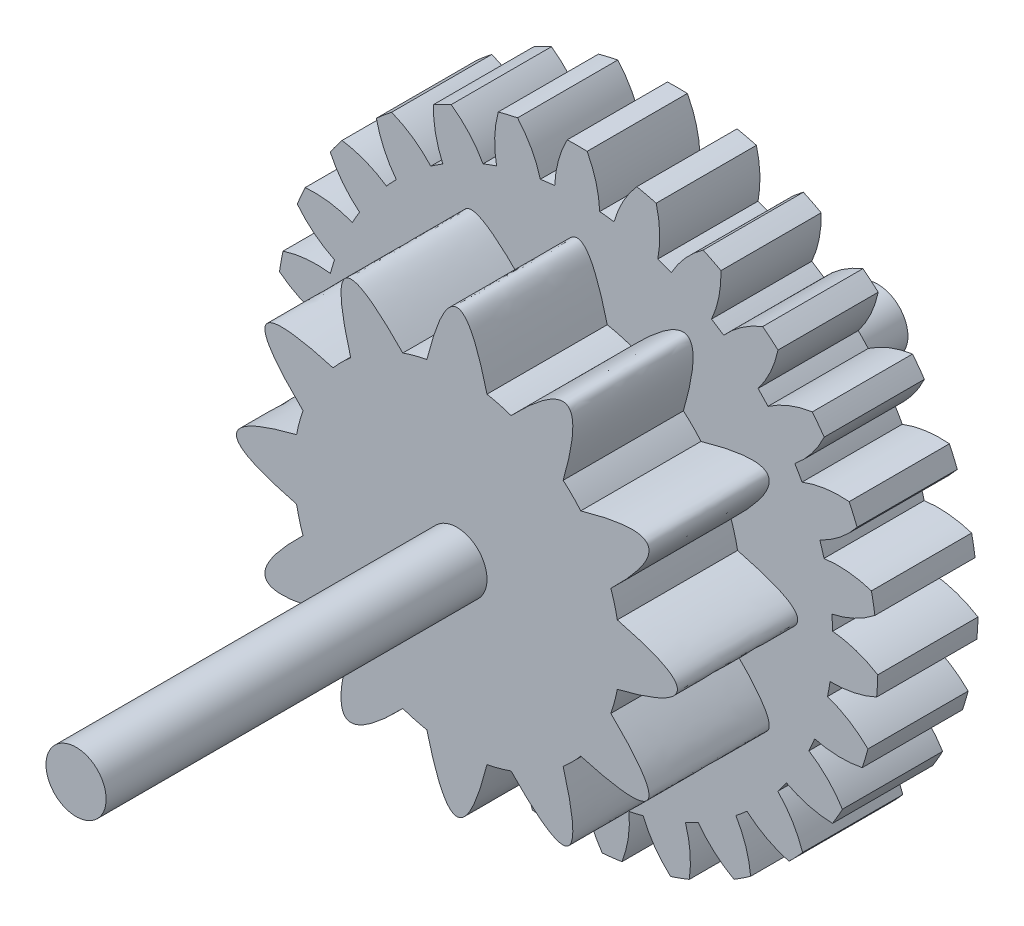
SolidWorks part; units mm, degrees
ref_plane "正面" through (0, 0, 0) normal (0, 0, 1) x (1, 0, 0)
ref_plane "平面" through (0, 0, 0) normal (0, 1, 0) x (1, 0, 0)
ref_plane "右側面" through (0, 0, 0) normal (1, 0, 0) x (0, 0, -1)
sketch "歯車パラメータ" plane through (0, 0, 0) normal (0, 0, 1) x (1, 0, 0)
  line L0 (0, 0) -> (1, 0)
  line L1 (1, 0) -> (1, -28)
  line L2 (1, -28) -> (21, -28)
  line L3 (21, -28) -> (21, -33)
  dimension "モジュール" = 1
  dimension "歯数" = 28
  dimension "圧力角" = 20
  dimension "歯車厚さ" = 5
sketch "ｽｹｯﾁ3" plane through (0, 0, 0) normal (0, 0, 1) x (1, 0, 0)
  circle A0 centre (0, 0) radius 14 construction
  circle A1 centre (0, 0) radius 12.75
  dimension "ピッチ円直径" = 28
  dimension "歯底円直径" = 25.5
extrude "ﾎﾞｽ - 押し出し1" add sketch "ｽｹｯﾁ3" along normal mid plane 5
sketch "ｽｹｯﾁ4" plane through (0, 0, 2.5) normal (0, 0, 1) x (1, 0, 0)
  line L1 (-0.785, 14.3566) -> (4.1739, 12.4861)
  line L8 (0, 15) -> (0, 12.75) construction
  line L9 (0, -12.75) -> (0, -15) construction
  arc A0 (0.4963, 14.9918) -> (-0.4963, 14.9918) centre (0, 0) ccw
  arc A2 (-0.4963, 14.9918) -> (-1.1217, 12.7006) centre (4.1739, 12.4861) ccw
  circle A3 centre (0, 0) radius 12.75 construction
  arc A4 (0.4963, 14.9918) -> (1.1217, 12.7006) centre (-4.1739, 12.4861) cw
  circle A5 centre (0, 0) radius 13.1557 construction
  arc A6 (1.1217, 12.7006) -> (-1.1217, 12.7006) centre (0, 0) ccw
  circle A10 centre (0, 0) radius 12.75
  arc A11 (1.1217, 12.7006) -> (0, -12.75) centre (0, 0) ccw
  arc A13 (0.785, 14.3566) -> (-0.785, 14.3566) centre (0, 0) ccw construction
  dimension "歯先円直径" = 30
  dimension "基礎円直径" = 26.3114
  dimension "歯型" = 5.3
  dimension "D1" = 1.57
  dimension "D2" = 0
extrude "ﾎﾞｽ - 押し出し2" add sketch "ｽｹｯﾁ4" against normal up to surface (5 mm away) contours A4 A0 A2 A6 up to face at (12.75, 0, -2.5)
pattern_circular "円形ﾊﾟﾀｰﾝ1" count 27 over 360 about axis through (0, 0, 2.5) along (0, 0, -1) of "ﾎﾞｽ - 押し出し2" reverse direction yes
sketch "ｽｹｯﾁ5" plane through (0, 0, 2.5) normal (0, 0, 1) x (1, 0, 0)
  circle A0 centre (0, 0) radius 1.5
  dimension "D1" = 3
extrude "ｶｯﾄ - 押し出し1" cut sketch "ｽｹｯﾁ5" against normal blind 10
sketch "ｽｹｯﾁ8" plane through (0, 0, 2.5) normal (0, 0, 1) x (1, 0, 0)
  line L0 (0, 8) -> (0, 11)
  line L1 (0, 8) -> (1.5, 8)
  line L2 (0, 8) -> (-1.5, 8)
  circle A0 centre (0, 0) radius 8
  circle A1 centre (0, 0) radius 8.1394
  circle A2 centre (0, 0) radius 1.5
  spline S0 degree 2 poles (-1.5, 8) (0, 14) (1.5, 8) knots 0 0 0 1 1 1
  dimension "D1" = 16
  dimension "D5" = 3
  dimension "D2" = 3
  dimension "D3" = 1.5
  dimension "D4" = 1.5
extrude "ﾎﾞｽ - 押し出し3" add sketch "ｽｹｯﾁ8" along normal blind 6 separate body contours S0 A1 L0 | A1 | A2 | L2 S0 L1 region at (-0.5625, 9.2559, 2.5)
ref_axis "軸5" through (0, 0, 5.9) along (0, 0, -1)
pattern_circular "円形ﾊﾟﾀｰﾝ3" count 12 over 360 about axis through (0, 0, 5.9) along (0, 0, -1) of bodies 107
combine bodies "組み合わせ1" bodies to combine 104 107 108 109 110 111 112 113 114 115 116 117 118
sketch "ｽｹｯﾁ9" plane through (0, 0, -2.5) normal (0, 0, -1) x (-1, 0, 0)
  circle A0 centre (0, 0) radius 1.5
  dimension "D1" = 3
extrude "ﾎﾞｽ - 押し出し4" add sketch "ｽｹｯﾁ9" along normal blind 10 separate body
extrude "ﾎﾞｽ - 押し出し5" add sketch "ｽｹｯﾁ9<2>" against normal blind 30
sketch "ｽｹｯﾁ9<2>" plane through (0, 0, -2.5) normal (0, 0, -1) x (-1, 0, 0) same geometry as "ｽｹｯﾁ9"
equation "\"ピッチ円直径@ｽｹｯﾁ3\"=\"モジュール@歯車パラメータ\"*\"歯数@歯車パラメータ\""
equation "\"歯底円直径@ｽｹｯﾁ3\"=\"ピッチ円直径@ｽｹｯﾁ3\"-2.5*\"モジュール@歯車パラメータ\""
equation "\"D1@ﾎﾞｽ - 押し出し1\"=\"歯車厚さ@歯車パラメータ\""
equation "\"歯型@ｽｹｯﾁ4\"=\"ピッチ円直径@ｽｹｯﾁ3\"/5-0.3"
